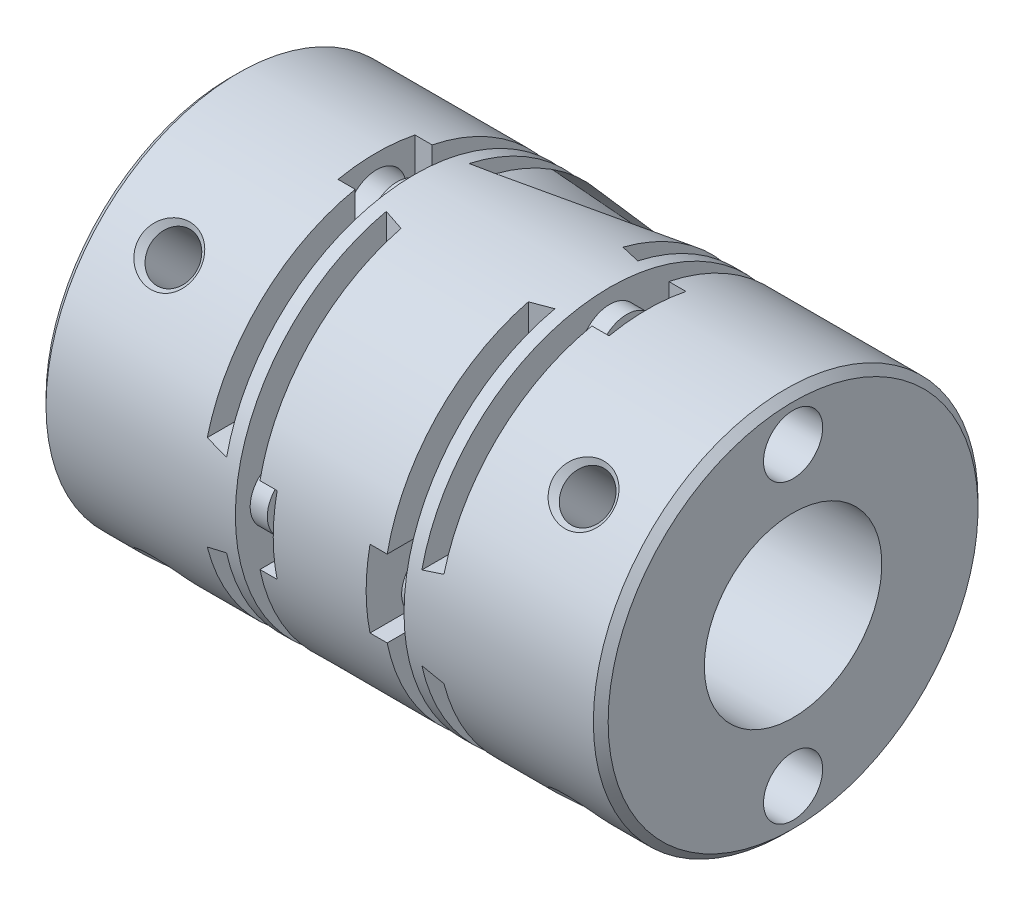
SolidWorks part; units mm, degrees
ref_plane "Front Plane" through (0, 0, 0) normal (0, 0, 1) x (1, 0, 0)
ref_plane "Top Plane" through (0, 0, 0) normal (0, 1, 0) x (1, 0, 0)
ref_plane "Right Plane" through (0, 0, 0) normal (1, 0, 0) x (0, 0, -1)
ref_plane "Plane1" through (0, 0, 0) normal (0, 0, 1) x (1, 0, 0)
sketch "Sketch1" plane through (0, 0, 0) normal (0, 0, 1) x (1, 0, 0)
  line L0 (0, 2.5) -> (5.5, 2.5)
  line L1 (5.5, 2.5) -> (5.5, 3.5)
  line L2 (5.5, 3.5) -> (6.2, 3.5)
  line L3 (6.2, 3.5) -> (6.2, 3)
  line L4 (6.2, 3) -> (6.65, 3)
  line L5 (6.65, 3) -> (6.65, 3.5)
  line L6 (6.65, 3.5) -> (7.35, 3.5)
  line L7 (7.35, 3.5) -> (7.35, 2.75)
  line L8 (7.35, 2.75) -> (11.65, 2.75)
  line L9 (11.65, 2.75) -> (11.65, 3.5)
  line L10 (11.65, 3.5) -> (12.35, 3.5)
  line L11 (12.35, 3.5) -> (12.35, 3)
  line L12 (12.35, 3) -> (12.8, 3)
  line L13 (12.8, 3) -> (12.8, 3.5)
  line L14 (12.8, 3.5) -> (13.5, 3.5)
  line L15 (13.5, 3.5) -> (13.5, 3)
  line L16 (13.5, 3) -> (19, 3)
  line L17 (19, 3) -> (19, 6.25)
  line L18 (19, 6.25) -> (18.75, 6.5)
  line L19 (18.75, 6.5) -> (0.25, 6.5)
  line L20 (0.25, 6.5) -> (0, 6.25)
  line L21 (0, 6.25) -> (0, 2.5)
  line L22 (19, 0) -> (0, 0) construction
revolve "Revolve1" add sketch "Sketch1" angle 360 about L22 reverse direction yes
ref_plane "Plane2" through (2.5, 0, 0) normal (1, 0, 0) x (0, 0, -1)
sketch "Sketch2" plane through (2.5, 0, 0) normal (1, 0, 0) x (0, 0, -1)
  line L0 (-4.5962, 4.5962) -> (-3.8891, 5.3033)
  line L1 (-3.8891, 5.3033) -> (-3.8891, 4.9971)
  line L2 (-3.8891, 4.9971) -> (0.554, 0.554)
  line L3 (0.554, 0.554) -> (0, 0)
  line L4 (0, 0) -> (-4.5962, 4.5962)
  line L5 (0, 0) -> (-4.5962, 4.5962) construction
revolve "Cut-Revolve1" cut sketch "Sketch2" angle 360 about L5 reverse direction yes
ref_plane "Plane3" through (2.5, 0, 0) normal (1, 0, 0) x (0, 0, -1)
sketch "Sketch3" plane through (2.5, 0, 0) normal (1, 0, 0) x (0, 0, -1)
  line L0 (-4.5962, -4.5962) -> (-5.3033, -3.8891)
  line L1 (-5.3033, -3.8891) -> (-4.9971, -3.8891)
  line L2 (-4.9971, -3.8891) -> (-0.554, 0.554)
  line L3 (-0.554, 0.554) -> (0, 0)
  line L4 (0, 0) -> (-4.5962, -4.5962)
  line L5 (0, 0) -> (-4.5962, -4.5962) construction
revolve "Cut-Revolve2" cut sketch "Sketch3" angle 360 about L5 reverse direction yes
ref_plane "Plane4" through (16.5, 0, 0) normal (1, 0, 0) x (0, 0, -1)
sketch "Sketch4" plane through (16.5, 0, 0) normal (1, 0, 0) x (0, 0, -1)
  line L0 (-4.5962, 4.5962) -> (-3.8891, 5.3033)
  line L1 (-3.8891, 5.3033) -> (-3.8891, 4.9971)
  line L2 (-3.8891, 4.9971) -> (0.554, 0.554)
  line L3 (0.554, 0.554) -> (0, 0)
  line L4 (0, 0) -> (-4.5962, 4.5962)
  line L5 (0, 0) -> (-4.5962, 4.5962) construction
revolve "Cut-Revolve3" cut sketch "Sketch4" angle 360 about L5 reverse direction yes
ref_plane "Plane5" through (16.5, 0, 0) normal (1, 0, 0) x (0, 0, -1)
sketch "Sketch5" plane through (16.5, 0, 0) normal (1, 0, 0) x (0, 0, -1)
  line L0 (-4.5962, -4.5962) -> (-5.3033, -3.8891)
  line L1 (-5.3033, -3.8891) -> (-4.9971, -3.8891)
  line L2 (-4.9971, -3.8891) -> (-0.554, 0.554)
  line L3 (-0.554, 0.554) -> (0, 0)
  line L4 (0, 0) -> (-4.5962, -4.5962)
  line L5 (0, 0) -> (-4.5962, -4.5962) construction
revolve "Cut-Revolve4" cut sketch "Sketch5" angle 360 about L5 reverse direction yes
ref_plane "Plane6" through (0, 0, 0) normal (0, 0, 1) x (1, 0, 0)
sketch "Sketch6" plane through (0, 0, 0) normal (0, 0, 1) x (1, 0, 0)
  line L0 (5.5, 7) -> (5.5, 1.6)
  line L1 (5.5, 1.6) -> (6.2, 1.4)
  line L2 (6.2, 1.4) -> (6.2, 6.5)
  line L3 (6.2, 6.5) -> (12.8, 6.5)
  line L4 (12.8, 6.5) -> (12.8, 1.4)
  line L5 (12.8, 1.4) -> (13.5, 1.6)
  line L6 (13.5, 1.6) -> (13.5, 7)
  line L7 (13.5, 7) -> (5.5, 7)
extrude "Cut-Extrude1" cut sketch "Sketch6" against normal blind 6.5 and the other way blind 6.5
ref_plane "Plane7" through (0, 0, 0) normal (0, 0, 1) x (1, 0, 0)
sketch "Sketch7" plane through (0, 0, 0) normal (0, 0, 1) x (1, 0, 0)
  line L0 (5.5, -7) -> (13.5, -7)
  line L1 (13.5, -7) -> (13.5, -1.6)
  line L2 (13.5, -1.6) -> (12.8, -1.4)
  line L3 (12.8, -1.4) -> (12.8, -6.5)
  line L4 (12.8, -6.5) -> (6.2, -6.5)
  line L5 (6.2, -6.5) -> (6.2, -1.4)
  line L6 (6.2, -1.4) -> (5.5, -1.6)
  line L7 (5.5, -1.6) -> (5.5, -7)
extrude "Cut-Extrude2" cut sketch "Sketch7" against normal blind 6.5 and the other way blind 6.5
ref_plane "Plane8" through (0, 0, 0) normal (0, 1, 0) x (1, 0, 0)
sketch "Sketch8" plane through (0, 0, 0) normal (0, 1, 0) x (1, 0, 0)
  line L0 (6.65, 7) -> (6.65, 1.4)
  line L1 (6.65, 1.4) -> (7.35, 1.6)
  line L2 (7.35, 1.6) -> (7.35, 6.5)
  line L3 (7.35, 6.5) -> (11.65, 6.5)
  line L4 (11.65, 6.5) -> (11.65, 1.6)
  line L5 (11.65, 1.6) -> (12.35, 1.4)
  line L6 (12.35, 1.4) -> (12.35, 7)
  line L7 (12.35, 7) -> (6.65, 7)
extrude "Cut-Extrude3" cut sketch "Sketch8" against normal blind 6.5 and the other way blind 6.5
ref_plane "Plane9" through (0, 0, 0) normal (0, 1, 0) x (1, 0, 0)
sketch "Sketch9" plane through (0, 0, 0) normal (0, 1, 0) x (1, 0, 0)
  line L0 (6.65, -7) -> (12.35, -7)
  line L1 (12.35, -7) -> (12.35, -1.4)
  line L2 (12.35, -1.4) -> (11.65, -1.6)
  line L3 (11.65, -1.6) -> (11.65, -6.5)
  line L4 (11.65, -6.5) -> (7.35, -6.5)
  line L5 (7.35, -6.5) -> (7.35, -1.6)
  line L6 (7.35, -1.6) -> (6.65, -1.4)
  line L7 (6.65, -1.4) -> (6.65, -7)
extrude "Cut-Extrude4" cut sketch "Sketch9" against normal blind 6.5 and the other way blind 6.5
ref_plane "Plane10" through (11.65, 0, 0) normal (1, 0, 0) x (0, 0, -1)
sketch "Sketch10" plane through (11.65, 0, 0) normal (1, 0, 0) x (0, 0, -1)
  line L0 (-6.5, -1.3) -> (-5, -1.3)
  line L1 (-5, 1.3) -> (-6.5, 1.3)
  line L2 (-6.5, 1.3) -> (-6.5, -1.3)
  arc A0 (-5, -1.3) -> (-5, 1.3) centre (-5, 0) ccw
extrude "Cut-Extrude5" cut sketch "Sketch10" against normal blind 0.58
ref_plane "Plane11" through (11.65, 0, 0) normal (1, 0, 0) x (0, 0, -1)
sketch "Sketch11" plane through (11.65, 0, 0) normal (1, 0, 0) x (0, 0, -1)
  line L0 (5, -1.3) -> (6.5, -1.3)
  line L1 (6.5, -1.3) -> (6.5, 1.3)
  line L2 (6.5, 1.3) -> (5, 1.3)
  arc A0 (5, 1.3) -> (5, -1.3) centre (5, 0) ccw
extrude "Cut-Extrude6" cut sketch "Sketch11" against normal blind 0.58
ref_plane "Plane12" through (7.35, 0, 0) normal (1, 0, 0) x (0, 0, -1)
sketch "Sketch12" plane through (7.35, 0, 0) normal (1, 0, 0) x (0, 0, -1)
  line L0 (-6.5, -1.3) -> (-5, -1.3)
  line L1 (-5, 1.3) -> (-6.5, 1.3)
  line L2 (-6.5, 1.3) -> (-6.5, -1.3)
  arc A0 (-5, -1.3) -> (-5, 1.3) centre (-5, 0) ccw
extrude "Cut-Extrude7" cut sketch "Sketch12" along normal blind 0.58
ref_plane "Plane13" through (7.35, 0, 0) normal (1, 0, 0) x (0, 0, -1)
sketch "Sketch13" plane through (7.35, 0, 0) normal (1, 0, 0) x (0, 0, -1)
  line L0 (5, -1.3) -> (6.5, -1.3)
  line L1 (6.5, -1.3) -> (6.5, 1.3)
  line L2 (6.5, 1.3) -> (5, 1.3)
  arc A0 (5, 1.3) -> (5, -1.3) centre (5, 0) ccw
extrude "Cut-Extrude8" cut sketch "Sketch13" along normal blind 0.58
ref_plane "Plane14" through (5.5, 0, 0) normal (1, 0, 0) x (0, 0, -1)
sketch "Sketch14" plane through (5.5, 0, 0) normal (1, 0, 0) x (0, 0, -1)
  line L0 (1.3, 5) -> (1.3, 6.5)
  line L1 (1.3, 6.5) -> (-1.3, 6.5)
  line L2 (-1.3, 6.5) -> (-1.3, 5)
  arc A0 (-1.3, 5) -> (1.3, 5) centre (0, 5) ccw
extrude "Cut-Extrude9" cut sketch "Sketch14" against normal blind 0.58
ref_plane "Plane15" through (5.5, 0, 0) normal (1, 0, 0) x (0, 0, -1)
sketch "Sketch15" plane through (5.5, 0, 0) normal (1, 0, 0) x (0, 0, -1)
  line L0 (-1.3, -5) -> (-1.3, -6.5)
  line L1 (-1.3, -6.5) -> (1.3, -6.5)
  line L2 (1.3, -6.5) -> (1.3, -5)
  arc A0 (1.3, -5) -> (-1.3, -5) centre (0, -5) ccw
extrude "Cut-Extrude10" cut sketch "Sketch15" against normal blind 0.58
ref_plane "Plane16" through (13.5, 0, 0) normal (1, 0, 0) x (0, 0, -1)
sketch "Sketch16" plane through (13.5, 0, 0) normal (1, 0, 0) x (0, 0, -1)
  line L0 (1.3, 5) -> (1.3, 6.5)
  line L1 (1.3, 6.5) -> (-1.3, 6.5)
  line L2 (-1.3, 6.5) -> (-1.3, 5)
  arc A0 (-1.3, 5) -> (1.3, 5) centre (0, 5) ccw
extrude "Cut-Extrude11" cut sketch "Sketch16" along normal blind 0.58
ref_plane "Plane17" through (13.5, 0, 0) normal (1, 0, 0) x (0, 0, -1)
sketch "Sketch17" plane through (13.5, 0, 0) normal (1, 0, 0) x (0, 0, -1)
  line L0 (-1.3, -5) -> (-1.3, -6.5)
  line L1 (-1.3, -6.5) -> (1.3, -6.5)
  line L2 (1.3, -6.5) -> (1.3, -5)
  arc A0 (1.3, -5) -> (-1.3, -5) centre (0, -5) ccw
extrude "Cut-Extrude12" cut sketch "Sketch17" along normal blind 0.58
ref_plane "Plane18" through (6.65, 0, 0) normal (1, 0, 0) x (0, 0, -1)
sketch "Sketch18" plane through (6.65, 0, 0) normal (1, 0, 0) x (0, 0, -1)
  circle A0 centre (-5, 0) radius 1
extrude "Boss-Extrude1" add sketch "Sketch18" along normal blind 0.58
ref_plane "Plane19" through (6.65, 0, 0) normal (1, 0, 0) x (0, 0, -1)
sketch "Sketch19" plane through (6.65, 0, 0) normal (1, 0, 0) x (0, 0, -1)
  circle A0 centre (5, 0) radius 1
extrude "Boss-Extrude2" add sketch "Sketch19" along normal blind 0.58
ref_plane "Plane20" through (6.2, 0, 0) normal (1, 0, 0) x (0, 0, -1)
sketch "Sketch20" plane through (6.2, 0, 0) normal (1, 0, 0) x (0, 0, -1)
  circle A0 centre (0, 5) radius 1
extrude "Boss-Extrude3" add sketch "Sketch20" against normal blind 0.58
ref_plane "Plane21" through (6.2, 0, 0) normal (1, 0, 0) x (0, 0, -1)
sketch "Sketch21" plane through (6.2, 0, 0) normal (1, 0, 0) x (0, 0, -1)
  circle A0 centre (0, -5) radius 1
extrude "Boss-Extrude4" add sketch "Sketch21" against normal blind 0.58
ref_plane "Plane22" through (12.35, 0, 0) normal (1, 0, 0) x (0, 0, -1)
sketch "Sketch22" plane through (12.35, 0, 0) normal (1, 0, 0) x (0, 0, -1)
  circle A0 centre (-5, 0) radius 1
extrude "Boss-Extrude5" add sketch "Sketch22" against normal blind 0.58
ref_plane "Plane23" through (12.35, 0, 0) normal (1, 0, 0) x (0, 0, -1)
sketch "Sketch23" plane through (12.35, 0, 0) normal (1, 0, 0) x (0, 0, -1)
  circle A0 centre (5, 0) radius 1
extrude "Boss-Extrude6" add sketch "Sketch23" against normal blind 0.58
ref_plane "Plane24" through (12.8, 0, 0) normal (1, 0, 0) x (0, 0, -1)
sketch "Sketch24" plane through (12.8, 0, 0) normal (1, 0, 0) x (0, 0, -1)
  circle A0 centre (0, 5) radius 1
extrude "Boss-Extrude7" add sketch "Sketch24" along normal blind 0.58
ref_plane "Plane25" through (12.8, 0, 0) normal (1, 0, 0) x (0, 0, -1)
sketch "Sketch25" plane through (12.8, 0, 0) normal (1, 0, 0) x (0, 0, -1)
  circle A0 centre (0, -5) radius 1
extrude "Boss-Extrude8" add sketch "Sketch25" along normal blind 0.58
ref_plane "Plane26" through (0, 0, 0) normal (1, 0, 0) x (0, 0, -1)
sketch "Sketch26" plane through (0, 0, 0) normal (1, 0, 0) x (0, 0, -1)
  circle A0 centre (0, 5) radius 1
extrude "Cut-Extrude13" cut sketch "Sketch26" along normal blind 5.5
ref_plane "Plane27" through (0, 0, 0) normal (1, 0, 0) x (0, 0, -1)
sketch "Sketch27" plane through (0, 0, 0) normal (1, 0, 0) x (0, 0, -1)
  circle A0 centre (0, -5) radius 1
extrude "Cut-Extrude14" cut sketch "Sketch27" along normal blind 5.5
ref_plane "Plane28" through (19, 0, 0) normal (1, 0, 0) x (0, 0, -1)
sketch "Sketch28" plane through (19, 0, 0) normal (1, 0, 0) x (0, 0, -1)
  circle A0 centre (0, 5) radius 1
extrude "Cut-Extrude15" cut sketch "Sketch28" against normal blind 5.5
ref_plane "Plane29" through (19, 0, 0) normal (1, 0, 0) x (0, 0, -1)
sketch "Sketch29" plane through (19, 0, 0) normal (1, 0, 0) x (0, 0, -1)
  circle A0 centre (0, -5) radius 1
extrude "Cut-Extrude16" cut sketch "Sketch29" against normal blind 5.5
